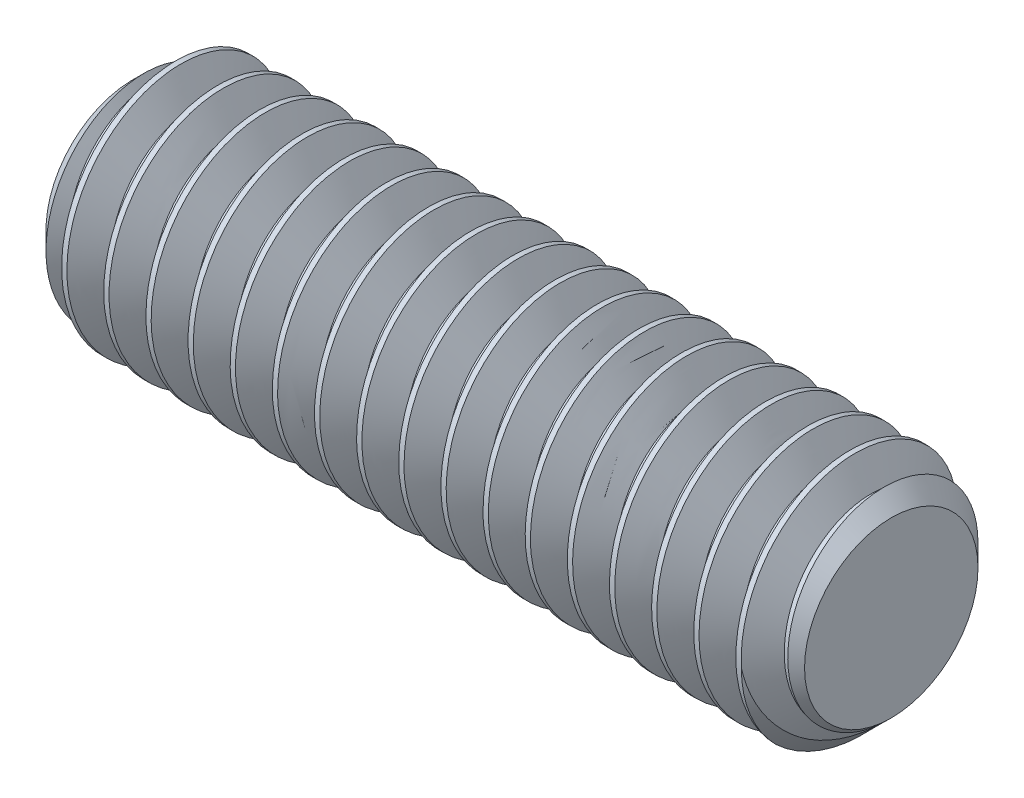
SolidWorks part; units mm, degrees
ref_plane "Front Plane" through (0, 0, 0) normal (0, 0, 1) x (1, 0, 0)
ref_plane "Top Plane" through (0, 0, 0) normal (0, 1, 0) x (1, 0, 0)
ref_plane "Right Plane" through (0, 0, 0) normal (1, 0, 0) x (0, 0, -1)
sketch "Sketch1" plane through (0, 0, 0) normal (0, 0, 1) x (1, 0, 0)
  line L0 (-12.7, 0) -> (12.7, 0) construction
  line L1 (12.7, 3.9624) -> (12.7, -3.9624) construction
  line L2 (-12.7, 3.9624) -> (-12.7, -3.9624) construction
  point P6 (7.7611, -3.9624)
  dimension "D1" = 4.9389
  dimension "Thread Diameter" = 7.9248
  dimension "Length" = 25.4
sketch "Sketch2" plane through (0, 0, 0) normal (1, 0, 0) x (0, 0, -1)
  circle A0 centre (0, 0) radius 3.9624
extrude "Boss-Extrude1" add sketch "Sketch2" against normal up to vertex (12.7 mm away) and the other way up to vertex (12.7 mm away) up to point (-12.7, 0, 0) other way up to point (12.7, 0, 0)
sketch "Sketch3" plane through (12.7, 0, 0) normal (1, 0, 0) x (0, 0, -1)
  circle A1 centre (0, 0) radius 3.9624
  circle A2 centre (0, 0) radius 3.9624
  dimension "D1" = 0
curve "Helix/Spiral1" pitch 1.4111 height 26.8111 turns 19 parameters "Pitch"=1.4111
chamfer "Chamfer1" distance 1.0583 angle 45 2 edges at (-12.7, 0, -3.9624) (12.7, 0, -3.9624)
sketch "Sketch4" plane through (0, 0, 0) normal (0, 0, 1) x (1, 0, 0)
  line L0 (12.6118, 4.1152) -> (13.3174, 2.8931) construction
  line L1 (13.3174, 2.8931) -> (14.0229, 4.1152) construction
  line L2 (14.0229, 4.1152) -> (12.6118, 4.1152) construction
  line L3 (13.3174, 4.1152) -> (13.3174, 3.9624) construction
  line L4 (13.3174, 2.8931) -> (13.3174, 3.0459) construction
  line L5 (13.2292, 3.0459) -> (13.4056, 3.0459) construction
  line L6 (12.7, 3.9624) -> (13.9347, 3.9624) construction
  line L7 (13.2292, 3.0459) -> (12.6559, 4.0388)
  line L8 (13.2292, 3.0459) -> (13.4056, 3.0459)
  line L9 (12.6559, 4.0388) -> (13.9788, 4.0388)
  line L10 (13.9788, 4.0388) -> (13.4056, 3.0459)
  point P13 (13.3174, 4.0388)
  dimension "D1" = 1.4111
  dimension "D2" = 0.1764
sweep "Cut-Sweep3" cut profiles "Sketch4" path "Helix/Spiral1" align with end faces yes
equation "\"D3@Helix/Spiral1\" = \"Length@Sketch1\"+\"Pitch@Helix/Spiral1\""
equation "\"D1@Chamfer1\" = \"Pitch@Helix/Spiral1\"*.75"
equation "\"D1@Sketch4\" = \"Pitch@Helix/Spiral1\""
equation "\"D2@Sketch4\" = \"D1@Sketch4\"/8"
equation "\"D1@Sketch1\" = \"Pitch@Helix/Spiral1\"*3.50"
